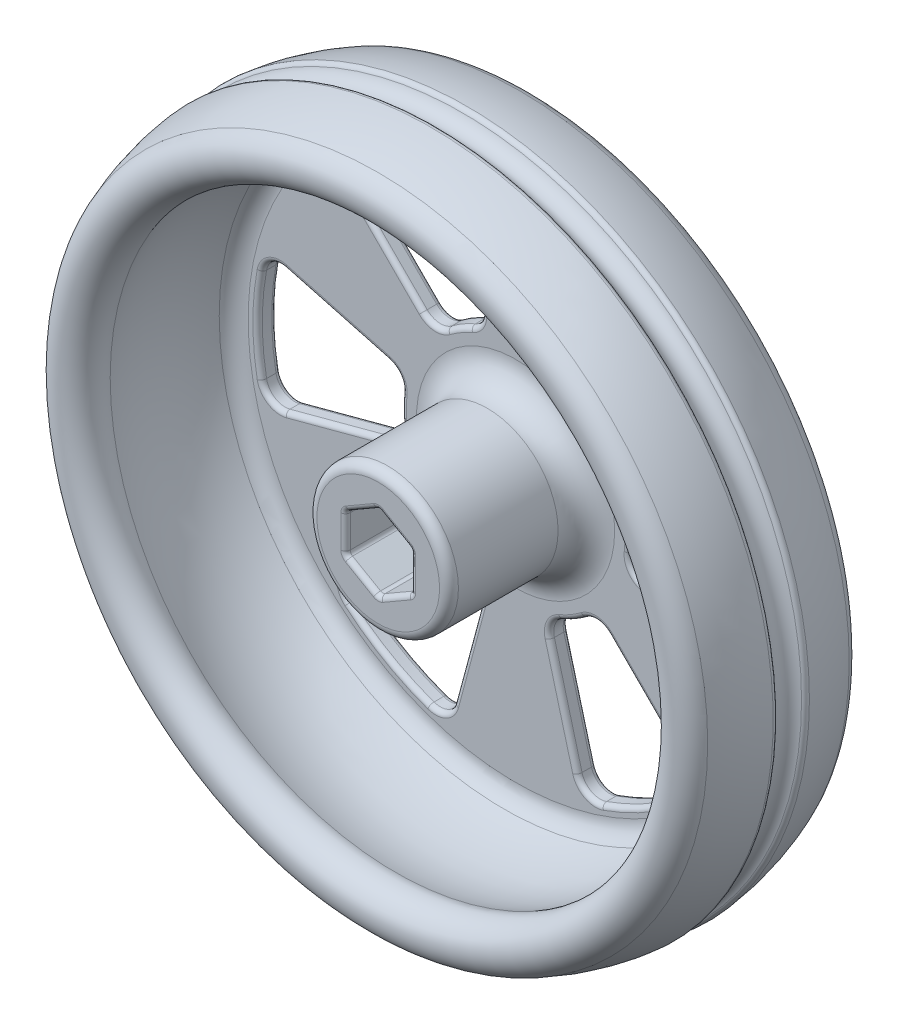
SolidWorks part; units mm, degrees
ref_plane "Front Plane" through (0, 0, 0) normal (0, 0, 1) x (1, 0, 0)
ref_plane "Top Plane" through (0, 0, 0) normal (0, 1, 0) x (1, 0, 0)
ref_plane "Right Plane" through (0, 0, 0) normal (1, 0, 0) x (0, 0, -1)
sketch "Sketch1" plane through (0, 0, 0) normal (0, 0, 1) x (1, 0, 0)
  line L5 (-2, -2) -> (2, 2) construction
  line L6 (-2, 2) -> (2, -2) construction
  line L7 (0, 4) -> (-3.4641, 2)
  line L8 (-3.4641, 2) -> (-3.4641, -2)
  line L9 (-3.4641, -2) -> (0, -4)
  line L10 (0, -4) -> (3.4641, -2)
  line L11 (3.4641, -2) -> (3.4641, 2)
  line L12 (3.4641, 2) -> (0, 4)
  circle A0 centre (0, 0) radius 4 construction
  circle A1 centre (0, 0) radius 7.5
  circle A2 centre (0, 0) radius 4 construction
  point P0 (0, 0)
  dimension "D3" = 8
  dimension "D1" = 15
extrude "Boss-Extrude1" add sketch "Sketch1" along normal blind 15
sketch "Sketch2" plane through (0, 0, 0) normal (0, 0, -1) x (-1, 0, 0)
  circle A1 centre (0, 0) radius 7.5
  circle A2 centre (0, 0) radius 7.5
  dimension "D1" = 0
sketch "Sketch3" plane through (0, 0, 0) normal (0, 1, 0) x (1, 0, 0)
  line L0 (0, 0) -> (0, -15)
  line L1 (0, -15) -> (-34.9205, -15) construction
  line L2 (-34.9205, -15) -> (-34.9205, 0) construction
  line L3 (-34.9205, 0) -> (0, 0) construction
  line L4 (0, -7.5) -> (-16.38, -7.5)
  line L5 (-7.5, -15) -> (7.5, -15) construction
  line L6 (-7.5, -15) -> (7.5, -15) construction
  line L7 (-36.38, -7.5) -> (-36.5, -7.5) construction
  line L8 (6, 0) -> (-7.5, 0)
  line L9 (-7.5, 0) -> (-7.5, -4.6916)
  line L10 (-7.5, 0) -> (-7.5, -15) construction
  line L11 (7.5, 0) -> (-7.5, 0) construction
  line L12 (-36.5, -7.5) -> (-36.5, 7.5) construction
  line L13 (0, 0) -> (0, 0.9733)
  line L14 (-32.6029, 1.5625) -> (0, 1.5625)
  line L15 (-32.6029, -0.4375) -> (0, -0.4375)
  line L16 (0, 0.9733) -> (0, 1.5625)
  circle A0 centre (-16.38, -7.5) radius 20
  circle A1 centre (-32.6029, -14.0625) radius 2.5
  circle A2 centre (-16.38, -7.5) radius 15
  circle A3 centre (-32.6029, -0.9375) radius 2.5
  circle A4 centre (-30.3782, -7.2778) radius 1
  circle A5 centre (-36.5, -7.5) radius 1.5
  spline S0 degree 3 poles (-30.3263, 0.0955) (-28.8778, -3.0967) (-1.9344, 0.1869) (-9.2863, 1.4092) (0, 0.9733) knots 0 0 0 0 0.24465 1 1 1 1
  spline S1 degree 1 poles (-34.8795, -1.9705) (-0.2344, -4.0212) knots 0 0 1 1 construction
  spline S2 degree 3 poles (-34.8795, -1.9705) (-34.631, -2.5181) (-33.9938, -3.5742) (-32.5346, -5.0655) (-30.931, -6.0139) (-29.2057, -6.6542) (-27.3756, -7.0643) (-25.2166, -7.2545) (-22.89, -7.2238) (-20.651, -7.0463) (-18.5417, -6.7866) (-16.0425, -6.4177) (-13.4519, -5.9953) (-10.9746, -5.525) (-9.1513, -5.1211) (-7.9581, -4.8183) (-6.6721, -4.4639) (-5.7282, -4.1701) (-5.2094, -4.0368) (-4.9433, -3.9873) (-4.4848, -3.9388) (-3.7649, -3.9176) (-2.9421, -3.9241) (-2.1941, -3.9418) (-1.4499, -3.9681) (-0.7855, -3.9959) (-0.4149, -4.0128) (-0.2344, -4.0212) knots 0 0 0 0 0.015625 0.03125 0.056327 0.071952 0.09375 0.125 0.15625 0.1875 0.21875 0.25 0.3125 0.375 0.4375 0.489231 0.520481 0.625 0.6875 0.75 0.8125 0.875 0.90625 0.9375 0.96875 0.984375 1 1 1 1
  point P34 (-35, -7.5)
  dimension "D1" = 40
  dimension "D6" = 2
  dimension "D9" = 3
  dimension "D2" = 35
  dimension "D3" = 2
  dimension "D8" = 15
  dimension "D4" = 5
  dimension "D5" = 5
revolve "Revolve1" add sketch "Sketch3" angle 360 about L0 region at (-1.8988, 0, -0.5382) region at (-6.4677, 0, -0.2612) region at (-2.0514, 0, -1.3062) region at (-33.4402, 0, 5.6138) region at (-32.1425, 0, 4.0507) region at (-17.9935, 0, -0.6111) region at (-32.6029, 0, 14.0625) region at (-29.9362, 0, -0.863) region at (-30.1441, 0, 0.3047) region at (-30.0066, 0, 0.8784) region at (-29.7989, 0, 0.5351)
fillet "Fillet1" radius 3 1 edges at (-7.5, 0, 0.4375)
sketch "Sketch4" plane through (0, 0, 0) normal (0, 0, 1) x (1, 0, 0)
  line L6 (3.4641, 2) -> (0, 4)
  line L7 (0, 4) -> (-3.4641, 2)
  line L8 (-3.4641, 2) -> (-3.4641, -2)
  line L9 (-3.4641, -2) -> (0, -4)
  line L10 (0, -4) -> (3.4641, -2)
  line L11 (3.4641, -2) -> (3.4641, 2)
  line L12 (3.4641, 2) -> (0, 4)
  line L13 (0, 4) -> (-3.4641, 2)
  line L14 (-3.4641, 2) -> (-3.4641, -2)
  line L15 (-3.4641, -2) -> (0, -4)
  line L16 (0, -4) -> (3.4641, -2)
  line L17 (3.4641, -2) -> (3.4641, 2)
  dimension "D1" = 0
extrude "Cut-Extrude1" cut sketch "Sketch4" against normal through all
fillet "Fillet2" radius 0.5 6 edges at (-3.4641, -2, 6.7188) (0, -4, 6.7188) (3.4641, -2, 6.7188) (3.4641, 2, 6.7188) (0, 4, 6.7188) (-3.4641, 2, 6.7188)
fillet "Fillet3" radius 0.5 24 edges at (-3.3971, 1.9613, 15) (-1.7321, 3, 15) (0, 3.9226, 15) (1.7321, 3, 15) (3.3971, 1.9613, 15) (3.4641, 0, 15) (3.3971, -1.9613, 15) (1.7321, -3, 15) (0, -3.9226, 15) (-1.7321, -3, 15) (-3.3971, -1.9613, 15) (-3.4641, 0, 15) (-3.3971, 1.9613, -1.5625) (-1.7321, 3, -1.5625) (0, 3.9226, -1.5625) (1.7321, 3, -1.5625) (3.3971, 1.9613, -1.5625) (3.4641, 0, -1.5625) (3.3971, -1.9613, -1.5625) (1.7321, -3, -1.5625) (0, -3.9226, -1.5625) (-1.7321, -3, -1.5625) (-3.3971, -1.9613, -1.5625) (-3.4641, 0, -1.5625)
fillet "Fillet4" radius 1 1 edges at (7.5, 0, 15)
fillet "Fillet5" radius 0.5 2 edges at (-36.3244, 0, 6.0103) (-36.3244, 0, 8.9897)
fillet "Fillet8" radius 2 1 edges at (-29.6133, 0, 0.4375)
sketch "Sketch6" plane through (0, 0, -1.5625) normal (0, 0, -1) x (-1, 0, 0)
  line L0 (0, 0) -> (26.4217, 7.0797)
  line L1 (0, 0) -> (26.4217, -7.0797)
  circle A2 centre (0, 0) radius 11.0976 construction
  circle A3 centre (0, 0) radius 11.0976 construction
  circle A5 centre (0, 0) radius 12.0976
  circle A7 centre (0, 0) radius 27.3537
  circle A8 centre (0, 0) radius 27.3537
  dimension "D3" = 30
  dimension "D1" = 1
  dimension "D2" = 1
extrude "Cut-Extrude2" cut sketch "Sketch6" against normal blind 10 contours A5 L1 L0 region at (-20.4732, 0, -1.5625)
fillet "Fillet6" radius 2 4 edges at (-11.6854, -3.1311, -0.5625) (-11.6854, 3.1311, -0.5625) (-26.4217, 7.0797, -0.5625) (-26.4217, -7.0797, -0.5625)
fillet "Fillet7" radius 0.5 16 edges at (-18.9465, -5.0767, 0.4375) (-12.3406, -2.8006, 0.4375) (-12.0976, 0, 0.4375) (-12.3406, 2.8006, 0.4375) (-12.3406, 2.8006, -1.5625) (-12.0976, 0, -1.5625) (-12.3406, -2.8006, -1.5625) (-18.9465, -5.0767, -1.5625) (-18.9465, 5.0767, 0.4375) (-18.9465, 5.0767, -1.5625) (-27.3537, 0, 0.4375) (-27.3537, 0, -1.5625) (-25.9987, -6.301, -1.5625) (-25.9987, 6.301, -1.5625) (-25.9987, 6.301, 0.4375) (-25.9987, -6.301, 0.4375)
ref_axis "Axis1" through (0, 0, 14) along (0, 0, -1)
pattern_circular "CirPattern4" count 6 over 360 about axis through (0, 0, 14) along (0, 0, -1) of "Cut-Extrude2", "Fillet7", "Fillet6"
